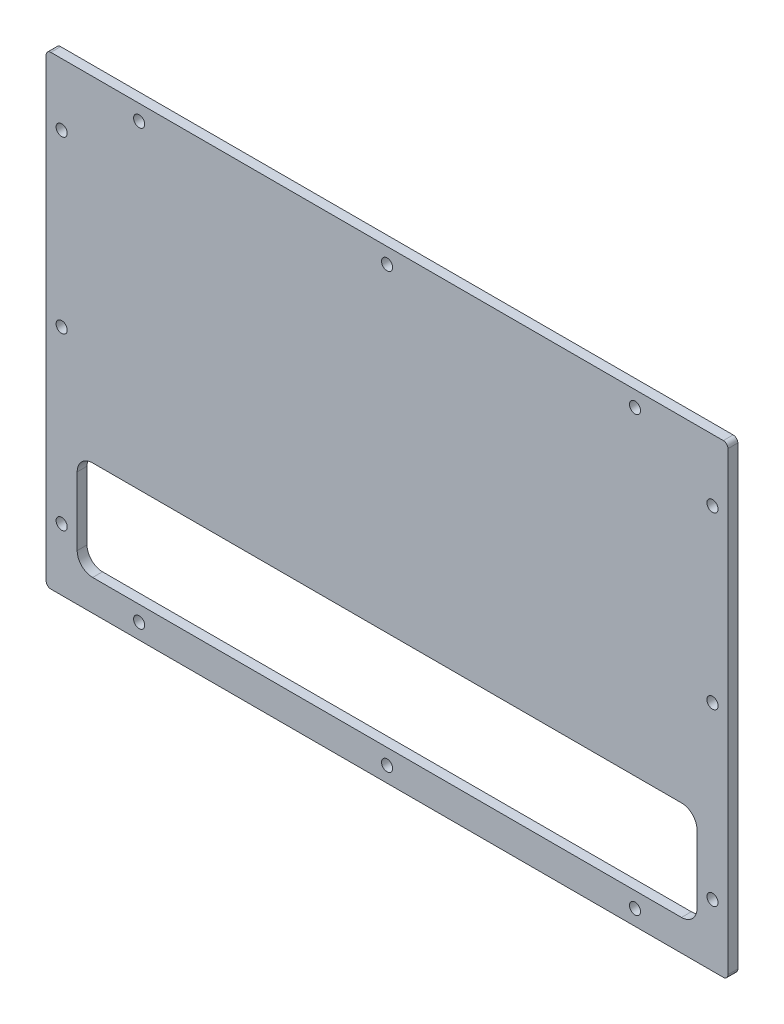
SolidWorks part; units mm, degrees
ref_plane "Front Plane" through (0, 0, 0) normal (0, 0, 1) x (1, 0, 0)
ref_plane "Top Plane" through (0, 0, 0) normal (0, 1, 0) x (1, 0, 0)
ref_plane "Right Plane" through (0, 0, 0) normal (1, 0, 0) x (0, 0, -1)
sketch "Sketch1" plane through (0, 0, 0) normal (0, 0, 1) x (1, 0, 0)
  line L0 (0, 0) -> (0, 75) construction
  line L1 (-110, -75) -> (110, -75)
  line L2 (-110, -75) -> (-110, 75)
  line L3 (-110, 75) -> (110, 75)
  line L4 (110, -75) -> (110, 75)
  line L5 (-110, -75) -> (110, 75) construction
  line L6 (-110, 75) -> (110, -75) construction
  line L15 (0, 0) -> (-110, 0) construction
  point P0 (0, 0)
  dimension "D1" = 220
  dimension "D2" = 150
extrude "Boss-Extrude1" add sketch "Sketch1" along normal blind 3.175 contours L3 L2 L1 L4 region at (0, 0, 0)
hole_wizard "M3 Clearance Hole1" positions "Sketch2" profile "Sketch3" hole size "M3" standard "ANSI Metric" end condition through all
sketch "Sketch2" plane through (0, 0, 3.175) normal (0, 0, 1) x (1, 0, 0)
  line L1 (-105, -70) -> (105, -70)
  line L2 (-105, -70) -> (-105, 70)
  line L3 (-105, 70) -> (105, 70)
  line L4 (105, -70) -> (105, 70)
  line L5 (-105, -70) -> (105, 70) construction
  line L6 (-105, 70) -> (105, -70) construction
  line L7 (-110, -75) -> (-110, 75) construction
  line L8 (-110, 75) -> (110, 75) construction
  point P2 (0, 0)
  point P113 (-80, 70)
  point P115 (80, 70)
  point P116 (0, 70)
  point P118 (-105, 55)
  point P120 (-105, 0)
  point P122 (-105, -55)
  point P124 (-80, -70)
  point P126 (0, -70)
  point P128 (80, -70)
  point P130 (105, -55)
  point P132 (105, 0)
  point P134 (105, 55)
  dimension "D1" = 5
  dimension "D2" = 5
  dimension "D3" = 80
  dimension "D4" = 80
  dimension "D5" = 55
  dimension "D6" = 55
sketch "Sketch3" plane through (0, 0, 3.175) normal (1, 0, 0) x (0, -1, 0)
  line L0 (0, 0) -> (0, 3.175)
  line L1 (0, 3.175) -> (1.8, 3.175)
  line L2 (1.8, 3.175) -> (1.8, 0)
  line L5 (1.8, 0) -> (0, 0)
  line L11 (0, -6.35) -> (0, 107.95) construction
  dimension "Thru Hole Dia." = 3.6
  dimension "Thru Hole Depth" = 3.175
sketch "Sketch4" plane through (0, 0, 3.175) normal (0, 0, 1) x (1, 0, 0)
  line L1 (-5, -5) -> (5, -5)
  line L2 (-5, -5) -> (-5, 5)
  line L3 (-5, 5) -> (5, 5)
  line L4 (5, -5) -> (5, 5)
  line L5 (-5, -5) -> (5, 5) construction
  line L6 (-5, 5) -> (5, -5) construction
  point P0 (0, 0)
  dimension "D1" = 10
  dimension "D2" = 10
extrude "Boss-Extrude2" add sketch "Sketch4" against normal through all
fillet "Fillet2" radius 1.5 4 edges at (-110, -75, 1.5875) (110, -75, 1.5875) (110, 75, 1.5875) (-110, 75, 1.5875)
sketch "Sketch5" plane through (0, 0, 3.175) normal (0, 0, 1) x (1, 0, 0)
  line L0 (-110, -73.5) -> (-110, 73.5) construction
  line L1 (-100, -65) -> (100, -65)
  line L2 (-100, -65) -> (-100, -33)
  line L3 (-100, -33) -> (100, -33)
  line L4 (100, -65) -> (100, -33)
  line L5 (-100, -65) -> (100, -33) construction
  line L6 (-100, -33) -> (100, -65) construction
  line L7 (-108.5, -75) -> (108.5, -75) construction
  line L8 (110, -73.5) -> (110, 73.5) construction
  point P0 (0, -49)
  dimension "D1" = 10
  dimension "D2" = 10
  dimension "D3" = 10
  dimension "D4" = 32
extrude "Cut-Extrude1" cut sketch "Sketch5" against normal through all
fillet "Fillet3" radius 5 4 edges at (-100, -65, 1.5875) (-100, -33, 1.5875) (100, -65, 1.5875) (100, -33, 1.5875)
